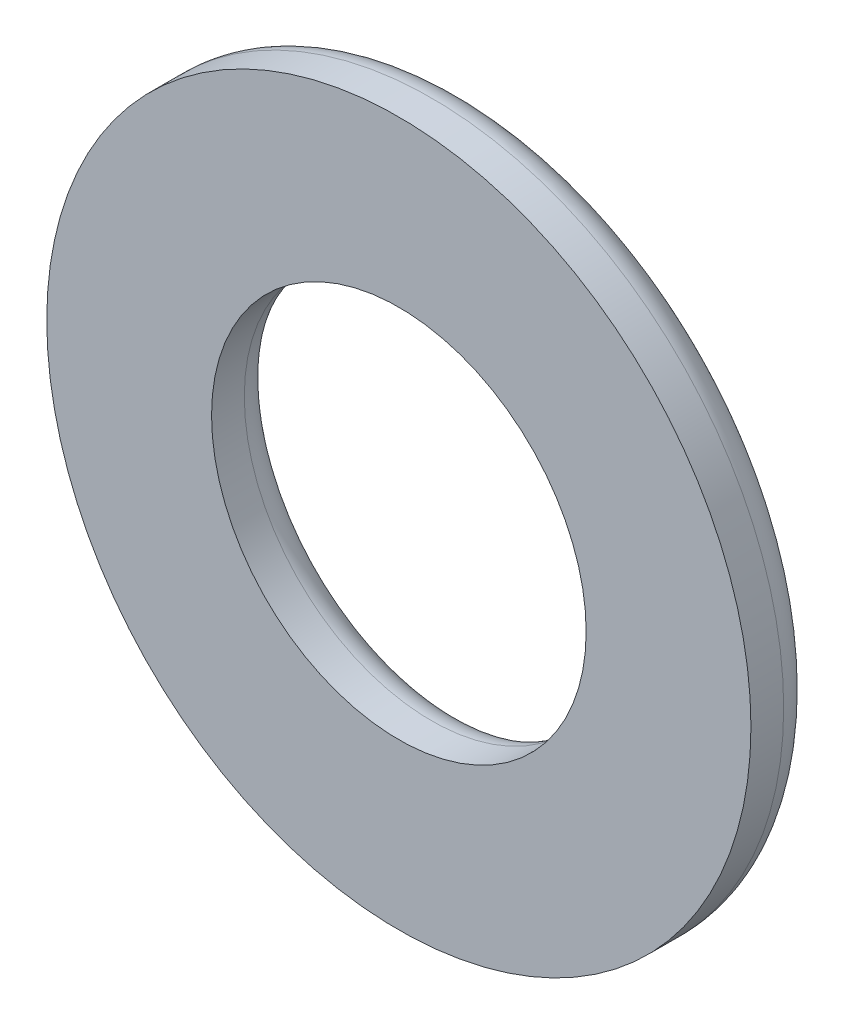
SolidWorks part; units mm, degrees
ref_plane "Front Plane" through (0, 0, 0) normal (0, 0, 1) x (1, 0, 0)
ref_plane "Top Plane" through (0, 0, 0) normal (0, 1, 0) x (1, 0, 0)
ref_plane "Right Plane" through (0, 0, 0) normal (1, 0, 0) x (0, 0, -1)
sketch "Sketch1" plane through (0, 0, 0) normal (0, 0, 1) x (1, 0, 0)
  line L0 (-6.35, 0) -> (6.35, 0) construction
  line L1 (0, 6.35) -> (0, -6.35) construction
  circle A0 centre (0, 0) radius 6.35 construction
  circle A1 centre (0, 0) radius 3.3782 construction
  point P4 (0, 0)
  point P8 (0, -3.3782)
  point P9 (3.3782, 0)
  point P10 (0, 3.3782)
  point P11 (-3.3782, 0)
  dimension "OD" = 12.7
  dimension "ID" = 6.7564
sketch "Sketch2" plane through (0, 0, 0) normal (1, 0, 0) x (0, 0, -1)
  line L0 (0.5906, 0) -> (-0.5906, 0) construction
  line L1 (0.5905, 6.35) -> (-0.5906, 6.35) construction
  line L2 (0.5905, 6.35) -> (0.5905, -6.35) construction
  line L3 (0.5905, -6.35) -> (-0.5906, -6.35) construction
  line L4 (-0.5906, 6.35) -> (-0.5906, -6.35) construction
  line L5 (-0.5906, 3.3782) -> (0.5905, 3.3782) construction
  line L6 (-0.5906, -3.3782) -> (0.5905, -3.3782) construction
  line L7 (-0.6477, 0) -> (0.6477, 0) construction
  line L8 (0, 6.35) -> (0, -6.35) construction
  point P6 (0, 0)
  point P17 (0, 0)
  point P18 (-0.5334, 0)
  point P21 (0.5334, 0)
  dimension "Thickness" = 1.1811
  dimension "Max Thickness Range" = 1.2954
  dimension "Min Thickness Range" = 1.0668
sketch "Sketch3" plane through (0, 0, 0) normal (0, 0, 1) x (1, 0, 0)
  line L0 (-6.35, 0) -> (6.35, 0) construction
  circle A0 centre (0, 0) radius 6.35
  circle A1 centre (0, 0) radius 3.3782
  circle A2 centre (0, 0) radius 6.35 construction
  circle A3 centre (0, 0) radius 3.3782 construction
extrude "Boss-Extrude1" add sketch "Sketch3" along normal up to vertex (0.5906 mm away) and the other way up to vertex (0.5906 mm away) up to point (0, 0, 0.5906) other way up to point (0, 0, -0.5906)
fillet "Fillet1" radius 0.5906 2 edges at (6.35, 0, -0.5906) (3.3782, 0, -0.5906)
equation "\"D1@Fillet1\"=\"Thickness@Sketch2\"*.5"
